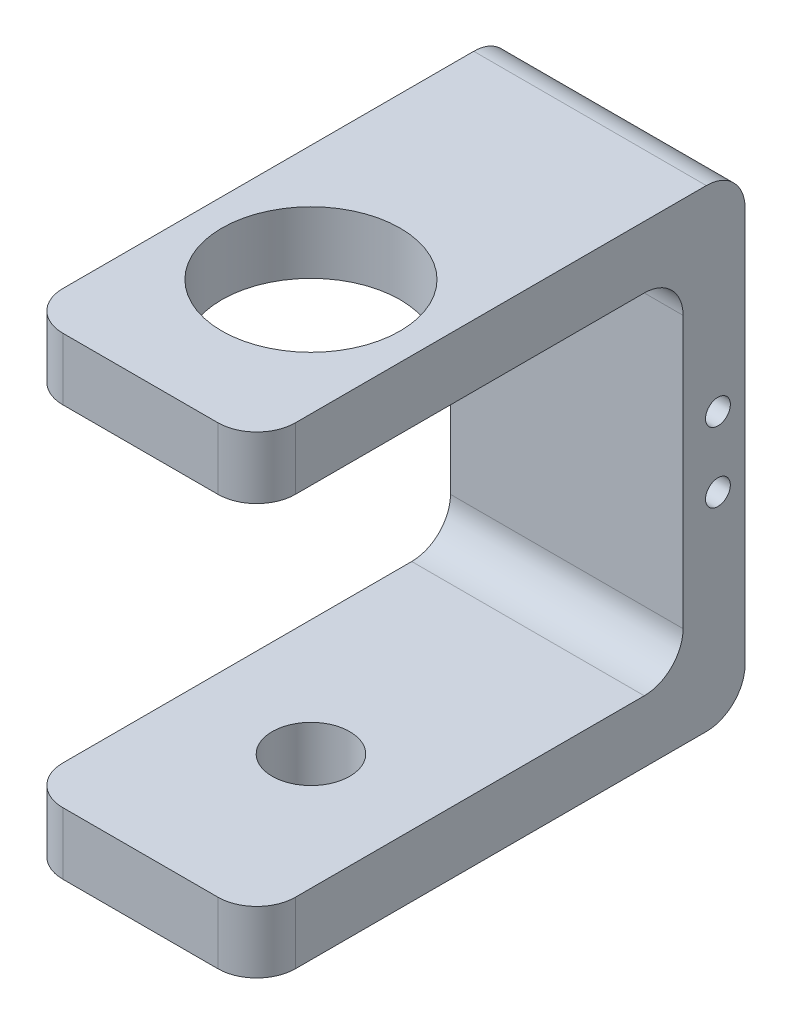
SolidWorks part; units mm, degrees
ref_plane "Front Plane" through (0, 0, 0) normal (0, 0, 1) x (1, 0, 0)
ref_plane "Top Plane" through (0, 0, 0) normal (0, 1, 0) x (1, 0, 0)
ref_plane "Right Plane" through (0, 0, 0) normal (1, 0, 0) x (0, 0, -1)
sketch "Sketch1" plane through (0, 0, 0) normal (1, 0, 0) x (0, 0, -1)
  line L0 (0, 0) -> (55, 0)
  line L1 (55, 0) -> (55, -45)
  line L2 (55, -45) -> (0, -45)
  line L3 (0, -45) -> (0, -53)
  line L4 (0, -53) -> (63, -53)
  line L5 (63, -53) -> (63, 8)
  line L6 (63, 8) -> (0, 8)
  line L7 (0, 8) -> (0, 0)
  dimension "D1" = 55
  dimension "D2" = 45
  dimension "D3" = 8
  dimension "D4" = 8
extrude "Boss-Extrude1" add sketch "Sketch1" along normal blind 30 contours L0 L1 L2 L3 L4 L5 L6 L7
sketch "Sketch2" plane through (0, 8, 0) normal (0, 1, 0) x (1, 0, 0)
  line L0 (30, 0) -> (0, 0) construction
  circle A0 centre (15, 22) radius 11.5
  point P2 (15, 0)
  dimension "D1" = 23
  dimension "D2" = 22
extrude "Cut-Extrude1" cut sketch "Sketch2" against normal up to next
sketch "Sketch3" plane through (0, -45, 0) normal (0, 1, 0) x (1, 0, 0)
  circle A0 centre (15, 22) radius 5
  circle A1 centre (15, 22) radius 11.5 construction
  dimension "D1" = 10
extrude "Cut-Extrude2" cut sketch "Sketch3" against normal up to next contours A0
sketch "Sketch4" plane through (30, 0, 0) normal (1, 0, 0) x (0, 0, -1)
  line L0 (63, -53) -> (63, 8) construction
  circle A2 centre (59.5, -27) radius 1.6
  circle A3 centre (59.5, -18) radius 1.6
  point P2 (0, 0)
  point P3 (0, 0)
  point P6 (63, -22.5)
  dimension "D1" = 9
  dimension "D4" = 3.2
  dimension "D2" = 3.5
  dimension "D3" = 4.5
extrude "Cut-Extrude3" cut sketch "Sketch4" against normal up to next contours A2 | A3 region at (30, -27, -59.5)
fillet "Fillet1" radius 5 6 edges at (15, -53, -63) (15, 8, -63) (0, -49, 0) (0, 4, 0) (30, -49, 0) (30, 4, 0)
fillet "Fillet2" radius 5 2 edges at (15, 0, -55) (15, -45, -55)
